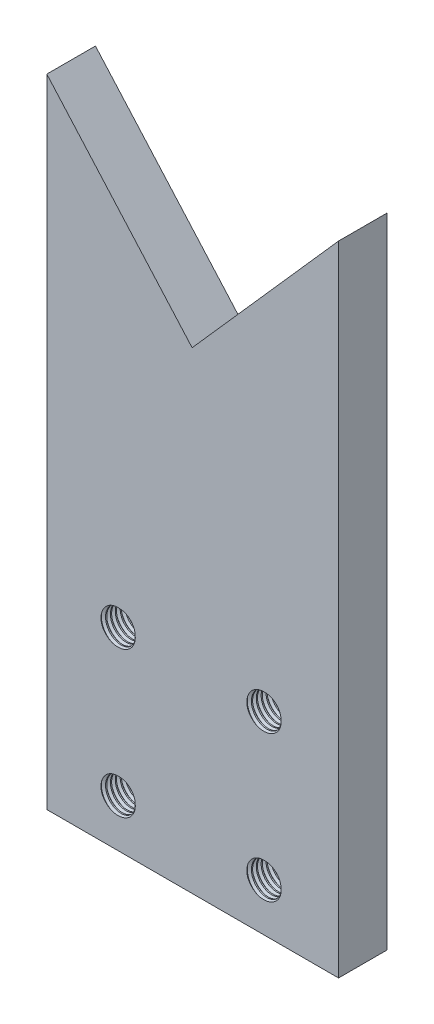
SolidWorks part; units mm, degrees
ref_plane "Front Plane" through (0, 0, 0) normal (0, 0, 1) x (1, 0, 0)
ref_plane "Top Plane" through (0, 0, 0) normal (0, 1, 0) x (1, 0, 0)
ref_plane "Right Plane" through (0, 0, 0) normal (1, 0, 0) x (0, 0, -1)
sketch "Sketch1" plane through (0, 0, 0) normal (0, 0, 1) x (1, 0, 0)
  line L1 (-37.951, -67.6038) -> (38.249, -67.6038)
  line L5 (0, 55.8402) -> (38.249, 99.1033)
  line L7 (0, -55) -> (0, 55) construction
  line L23 (0, 55.8402) -> (-37.951, 98.7662)
  line L24 (38.249, -67.6038) -> (38.249, 99.1033)
  line L25 (-37.951, -67.6038) -> (-37.951, 98.7662)
  point P0 (0, 0)
  dimension "D1" = 41.48
  dimension "D2" = 41.48
  dimension "D3" = 123.444
  dimension "D4" = 76.2
  dimension "D5" = 166.37
extrude "Boss-Extrude1" add sketch "Sketch1" along normal blind 12.7
ref_axis "Axis1" through (0, -67.6038, 12.7) along (0, 1, 0)
sketch "Sketch2" plane through (0, 0, 12.7) normal (0, 0, 1) x (1, 0, 0)
  line L0 (0, -67.6038) -> (0, 55.8402) construction
  line L1 (-37.951, -67.6038) -> (38.249, -67.6038) construction
  circle A0 centre (19.05, -54.9038) radius 4.191
  dimension "D1" = 19.05
  dimension "D2" = 12.7
extrude "Cut-Extrude1" cut sketch "Sketch2" against normal through all
pattern_linear "LPattern1" count 2 spacing 38.1 along (0, 1, 0) count 2 spacing 38.1 along (-1, 0, 0) of "Cut-Extrude1"
thread "Thread1" pitch 1.27 method cut profile "Thread Profile1" start angle 0, offset 0, length 0, pitch 1.27, diameter 8.382
ref_plane "Plane1" through (23.241, -54.9038, 0) normal (0, -1, 0) x (1, 0, 0)
sketch "Thread Profile1" plane through (23.241, -54.9038, 0) normal (0, -1, 0) x (1, 0, 0)
  line L0 (0, 0) -> (0, 1.27) construction
  line L1 (0, 0) -> (0.6874, 0.3969)
  line L2 (0.6874, 0.3969) -> (0.6874, 0.5556)
  line L3 (0.6874, 0.5556) -> (0, 0.9525)
  line L4 (0.6874, 0.4762) -> (0, 0.4762) construction
  line L11 (0, 0) -> (0, 0.9525)
  point P2 (0, 0)
  dimension "Pitch" = 1.27
  dimension "Profile_Angle" = 60
  dimension "Profile_Land" = 0.1588
  dimension "Profile_Height" = 0.6874
pattern_linear "LPattern2" count 2 spacing 38.1 along (0, 1, 0) count 2 spacing 38.1 along (-1, 0, 0) of "Thread1"
